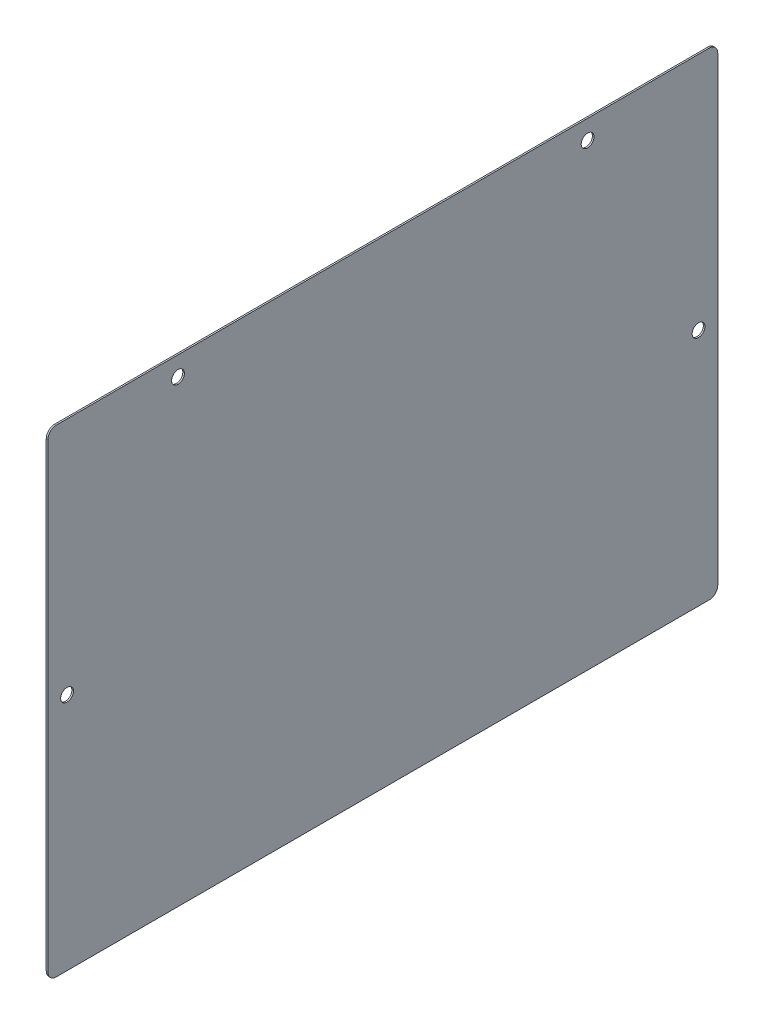
SolidWorks part; units mm, degrees
material "SH,Plain Carbon"
ref_plane "Front" through (0, 0, 0) normal (0, 0, 1) x (1, 0, 0)
ref_plane "Top" through (0, 0, 0) normal (0, 1, 0) x (1, 0, 0)
ref_plane "Right" through (0, 0, 0) normal (1, 0, 0) x (0, 0, -1)
sketch "Sketch1" plane through (0, 0, 0) normal (1, 0, 0) x (0, 0, -1)
  line L1 (249.2375, -177.8) -> (-249.2375, -177.8)
  line L2 (249.2375, -177.8) -> (249.2375, 177.8)
  line L3 (249.2375, 177.8) -> (-249.2375, 177.8)
  line L4 (-249.2375, -177.8) -> (-249.2375, 177.8)
  line L5 (249.2375, -177.8) -> (-249.2375, 177.8) construction
  line L6 (249.2375, 177.8) -> (-249.2375, -177.8) construction
  point P0 (0, 0)
  dimension "D1" = 498.475
  dimension "D2" = 355.6
base flange "Base-Flange1" sketch "Sketch1" thickness 1.1938 reverse thickness direction no parameters "D1"=1.4986
sketch "Sketch6" plane through (0, 0, 0) normal (1, 0, 0) x (0, 0, -1)
  line L0 (-249.2375, 177.8) -> (-249.2375, -177.8) construction
  line L1 (249.2375, 177.8) -> (-249.2375, 177.8) construction
  circle A0 centre (-152.4, 163.5125) radius 4.7625
  circle A1 centre (-234.95, 0) radius 4.7625
  dimension "D2" = 9.525
  dimension "D1" = 14.2875
  dimension "D3" = 14.2875
  dimension "D4" = 152.4
extrude "Cut-Extrude1" cut sketch "Sketch6" against normal up to next normal cut yes
mirror "Mirror1" about plane through (0, 0, 0) normal (0, 0, 1) of "Cut-Extrude1"
fillet "Fillet1" radius 6.35 4 edges at (-0.5969, -177.8, -249.2375) (-0.5969, 177.8, -249.2375) (-0.5969, -177.8, 249.2375) (-0.5969, 177.8, 249.2375)
other "LaserCutPropertyMigration-DeleteAfterThisAppears1"
sketch "Bend-Lines1" [suppressed] plane through (0, 0, 0) normal (0, 1, 0) x (1, 0, 0)
sketch "Bounding-Box1" [suppressed] plane through (0, 0, 0) normal (0, 1, 0) x (1, 0, 0)
sheet metal parameters "Sheet-Metal28" thickness 1.1938 parameters "D1"=1.4986
flat pattern "Flat-Pattern28" [suppressed]
sketch "Bend-Lines2" plane through (0, 0, 0) normal (0, 1, 0) x (1, 0, 0)
sketch3d "Bounding-Box2" [suppressed]
  line L0 (247.65, -177.8, 0) -> (-247.65, -177.8, 0) construction
  line L1 (247.65, 177.8, 0) -> (-247.65, 177.8, 0) construction
  line L2 (247.65, -177.8, 0) -> (247.65, 177.8, 0) construction
  line L3 (-247.65, -177.8, 0) -> (-247.65, 177.8, 0) construction
sheet metal parameters "Sheet-Metal29" thickness 1.1938 parameters "D1"=1.4986
flat pattern "Flat-Pattern28"
sketch "Bend-Lines2" plane through (0, 0, 0) normal (0, 1, 0) x (1, 0, 0)
sketch3d "Bounding-Box2" [suppressed]
  line L0 (-247.65, -177.8, 0) -> (247.65, -177.8, 0) construction
  line L1 (-247.65, 177.8, 0) -> (247.65, 177.8, 0) construction
  line L2 (-247.65, -177.8, 0) -> (-247.65, 177.8, 0) construction
  line L3 (247.65, -177.8, 0) -> (247.65, 177.8, 0) construction
sheet metal parameters "Sheet-Metal30" thickness 1.1938 parameters "D1"=1.4986
flat pattern "Flat-Pattern28"
sketch "Bend-Lines2" plane through (0, 0, 0) normal (0, 1, 0) x (1, 0, 0)
sketch3d "Bounding-Box2" [suppressed]
  line L0 (-249.2375, 177.8, 0) -> (249.2375, 177.8, 0) construction
  line L1 (-249.2375, -177.8, 0) -> (249.2375, -177.8, 0) construction
  line L2 (-249.2375, 177.8, 0) -> (-249.2375, -177.8, 0) construction
  line L3 (249.2375, 177.8, 0) -> (249.2375, -177.8, 0) construction
equation "\"Total Cutting Length\"= \"Cutting Length-Outer\" + \"Cutting Length-Inner\""
equation "\"Amount in ft^2\"= \"Bounding Box Area-Blank\" / 144"
